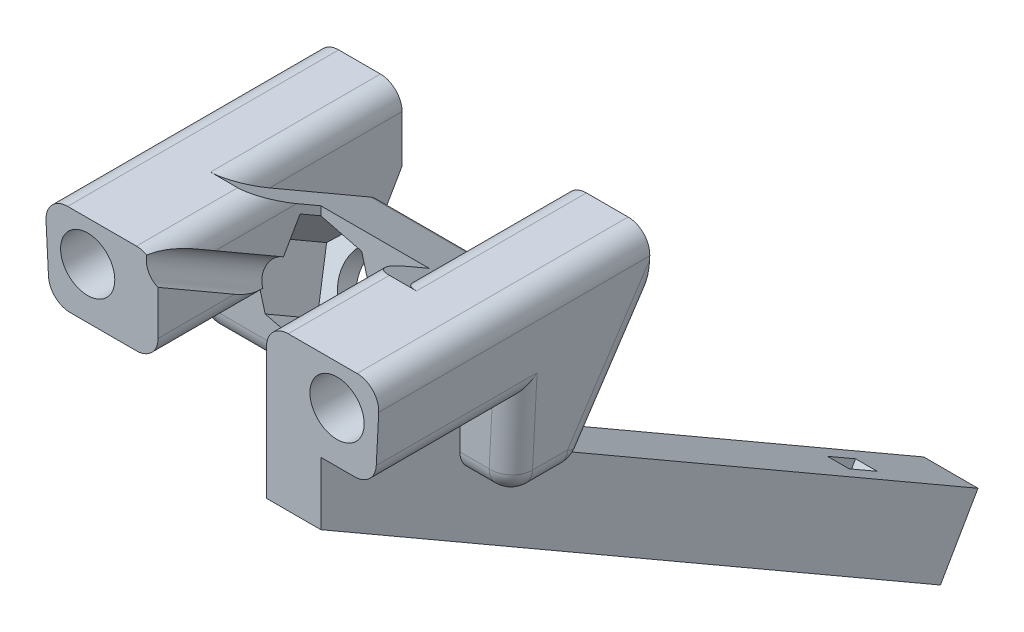
SolidWorks part; units mm, degrees
ref_plane "Alzado" through (0, 0, 0) normal (0, 0, 1) x (1, 0, 0)
ref_plane "Planta" through (0, 0, 0) normal (0, 1, 0) x (1, 0, 0)
ref_plane "Vista lateral" through (0, 0, 0) normal (1, 0, 0) x (0, 0, -1)
sketch "Croquis1" plane through (0, 0, 0) normal (0, 0, 1) x (1, 0, 0)
  line L0 (-15.1222, -77.6726) -> (-16.327, -54.7197)
  line L2 (15.1222, -77.6726) -> (16.327, -54.7197)
  line L4 (16.327, -54.7197) -> (-16.327, -54.7197)
  line L5 (-9.306, -78.3777) -> (-6.6466, -69.6276)
  line L6 (-3.7763, -67.5) -> (3.7763, -67.5)
  line L7 (6.6466, -69.6276) -> (9.306, -78.3777)
  circle A0 centre (-11.5, -75) radius 1.4876
  circle A1 centre (11.5, -75) radius 1.5
  arc A2 (-12.7397, -80.452) -> (-15.1222, -77.6726) centre (-12.1263, -77.5153) cw
  arc A3 (-12.7397, -80.452) -> (-9.306, -78.3777) centre (-12.1764, -77.5053) ccw
  arc A4 (-6.6466, -69.6276) -> (-3.7763, -67.5) centre (-3.7763, -70.5) cw
  arc A5 (3.7763, -67.5) -> (6.6466, -69.6276) centre (3.7763, -70.5) cw
  arc A6 (9.306, -78.3777) -> (12.7397, -80.452) centre (12.1764, -77.5053) ccw
  arc A7 (12.7397, -80.452) -> (15.1222, -77.6726) centre (12.1263, -77.5153) ccw
ref_plane "Plano1" through (0, 0, 0) normal (0, 0, 1) x (1, 0, 0)
sketch "Croquis2" plane through (0, 0, 0) normal (0, 0, 1) x (1, 0, 0)
  line L3 (15.4559, -71.3146) -> (-15.4559, -71.3146)
  line L4 (-3.7763, -67.5) -> (3.7763, -67.5) construction
  line L20 (15.1222, -77.6726) -> (15.4559, -71.3146)
  line L21 (-15.1222, -77.6726) -> (-14.5973, -87.6726)
  line L22 (15.1222, -77.6726) -> (6, -87.6726) construction
  line L23 (6, -87.6726) -> (-6, -87.6726)
  line L24 (0, -87.6726) -> (0, -67.5) construction
  line L25 (11.5, -72.5146) -> (11.5, -71.3146) construction
  line L26 (-11.5, -72.5146) -> (-11.5, -71.3146) construction
  line L27 (-15.1222, -77.6726) -> (-6, -87.6726) construction
  line L28 (-15.1222, -77.6726) -> (-15.4559, -71.3146)
  line L29 (-14.5973, -87.6726) -> (-6, -87.6726)
  line L30 (14.5973, -87.6726) -> (6, -87.6726)
  line L31 (15.1222, -77.6726) -> (14.5973, -87.6726)
  circle A4 centre (11.5, -75.0146) radius 2.5
  circle A5 centre (-11.5, -75.0146) radius 2.5
  point P11 (0, -78.4389)
  point P18 (0, -71.3146)
  dimension "D1" = 10
  dimension "D2" = 6
  dimension "D3" = 1.2
extrude "Saliente-Extruir1" add sketch "Croquis2" along normal blind 25
sketch "Croquis4" plane through (19.1465, -1.005, 0) normal (0.9986, -0.0524, 0) x (0, 0, -1)
  line L0 (5.0449, -68.0352) -> (5.0449, -99.8584)
  line L1 (5.0449, -99.8584) -> (-12.1656, -99.8584)
  line L2 (-9.729, -93.6242) -> (5.0449, -68.0352)
  line L4 (-25, -78.7869) -> (-25, -99.8584)
  line L5 (-25, -99.8584) -> (-12.1656, -99.8584)
  line L6 (-25, -78.7869) -> (-12.1656, -78.7869)
  line L8 (-12.1656, -78.7869) -> (-12.1656, -93.6242)
  line L9 (-12.1656, -93.6242) -> (-9.729, -93.6242)
  line L10 (0, -86.7869) -> (0, -70.4064) construction
  line L11 (-25, -86.7869) -> (0, -86.7869) construction
  point P10 (0, 0)
  point P11 (0, 0)
  point P12 (0, 0)
  point P15 (0, 0)
  dimension "D1" = 12.8344
  dimension "D2" = 30
  dimension "D3" = 12.1656
  dimension "D4" = 8
  dimension "D5" = 8
extrude "Cortar-Extruir1" cut sketch "Croquis4" along direction (1, 0, 0) on the side against the normal up to vertex (30.8693 mm away) up to point (-15.4559, -71.3146, 0)
sketch "Croquis5" plane through (0, -19.4582, -33.6563) normal (0, -0.5005, -0.8657) x (-1, 0, 0)
  line L0 (4.5973, -78.7943) -> (4.5973, -77.7943) construction
  line L2 (14.5973, -78.7943) -> (-14.5973, -78.7943) construction
  circle A0 centre (4.5973, -74.7943) radius 3
  point P4 (4.7149, -74.5677)
  point P5 (0, 0)
  point P6 (0, -74.7943)
  point P7 (0, 0)
  point P8 (7.1089, -74.0449)
  point P9 (0, 0)
  point P12 (7.5802, -74.7943)
  dimension "D1" = 1
  dimension "D2" = 6
  dimension "D3" = 10
extrude "Cortar-Extruir2" cut sketch "Croquis5" against normal blind 2
sketch "Croquis6" plane through (0, -18.4572, -31.9249) normal (0, -0.5005, -0.8657) x (-1, 0, 0)
  line L1 (3.0757, -79.5571) -> (7.9613, -78.4934)
  line L2 (7.9613, -78.4934) -> (9.4828, -73.7305)
  line L3 (9.4828, -73.7305) -> (6.1188, -70.0314)
  line L4 (6.1188, -70.0314) -> (1.2333, -71.0951)
  line L5 (1.2333, -71.0951) -> (-0.2883, -75.858)
  line L6 (-0.2883, -75.858) -> (3.0757, -79.5571)
  circle A0 centre (4.5973, -74.7943) radius 4.3301 construction
  dimension "D1" = 5
extrude "Cortar-Extruir3" cut sketch "Croquis6" against normal blind 10
sketch "Croquis8" plane through (0, -71.3146, 0) normal (0, 1, 0) x (1, 0, 0)
  line L2 (-5, -25) -> (5, -25)
  line L3 (-5, -25) -> (-5, -10)
  line L4 (-5, -10) -> (5, -10)
  line L5 (5, -25) -> (5, -10)
  line L11 (0, 0) -> (0, -25) construction
  line L12 (15.4559, 0) -> (-15.4559, 0) construction
  dimension "D1" = 5
  dimension "D2" = 15
  dimension "D3" = 10
extrude "Cortar-Extruir4" cut sketch "Croquis8" against normal blind 10
sketch "Croquis17" plane through (0, -19.4582, -33.6563) normal (0, -0.5005, -0.8657) x (-1, 0, 0)
  line L1 (-7.5, -61.0354) -> (7.5, -61.0354)
  line L2 (-7.5, -61.0354) -> (-7.5, -69.5824)
  line L3 (-7.5, -69.5824) -> (7.5, -69.5824)
  line L4 (7.5, -61.0354) -> (7.5, -69.5824)
  line L5 (0, -66.9256) -> (0, -56.6704) construction
  dimension "D1" = 15
  dimension "D2" = 7.5
extrude "Cortar-Extruir7" cut sketch "Croquis17" against normal blind 20
sketch "Croquis19" plane through (0, -19.4582, -33.6563) normal (0, -0.5005, -0.8657) x (-1, 0, 0)
  circle A0 centre (4.5973, -74.7943) radius 1.5
  dimension "D1" = 3
extrude "Cortar-Extruir9" cut sketch "Croquis19" against normal blind 30
sketch "Croquis20" plane through (5, -0.634, 0) normal (1, 0, 0) x (0, 0, -1)
  line L0 (-25, -78.7869) -> (-17.5618, -83.0813)
  line L1 (-12.1656, -79.0496) -> (-25, -79.0496) construction
  line L2 (-25, -79.0496) -> (-25, -70.6806) construction
  point P5 (0, 0)
  point P6 (0, 0)
  dimension "D1" = 30
sketch "Croquis21" plane through (0, 0, 25) normal (0, 0, 1) x (1, 0, 0)
  line L1 (10, -77.4689) -> (5, -77.4689)
  line L2 (10, -77.4689) -> (10, -85.4689)
  line L3 (10, -85.4689) -> (5, -85.4689)
  line L4 (5, -77.4689) -> (5, -85.4689)
  line L5 (5, -79.6836) -> (5, -71.3146) construction
  line L6 (5, -79.6836) -> (15.0166, -79.6836) construction
  point P4 (14, -77.5146)
  point P5 (0, 0)
  point P11 (0, 0)
  dimension "D1" = 8
  dimension "D2" = 5
extrude "Saliente-Extruir2" add sketch "Croquis21" along direction (0, -0.5, -0.866) on the side against the normal blind 70
fillet "Redondeo7" radius 2 19 edges at (-5, -79.6836, 20.0119) (0, -87.6726, 5.7815) (5, -71.3146, 20.3353) (7.5, -71.3146, 7.8353) (-5, -71.3146, 19.4337) (-7.5, -71.3146, 7.8353) (-15.4559, -71.3146, 12.5) (15.4559, -71.3146, 12.5) (0, -79.6976, 1.1708) (-14.8069, -83.6781, 12.1656) (-14.8597, -82.6726, 2.8907) (-14.5973, -87.6726, 8.9735) (-15.0166, -79.6836, 18.5828) (14.5973, -87.6726, 8.9735) (14.8597, -82.6726, 2.8907) (-4.7986, -87.6726, 12.1656) (12.2986, -87.6726, 12.1656) (14.8069, -83.6781, 12.1656) (15.0166, -79.6836, 18.5828)
sketch "Croquis27" plane through (10, 0, 0) normal (1, 0, 0) x (0, 0, -1)
  line L0 (36.1607, -111.5355) -> (31.3411, -119.8832)
  line L2 (31.3411, -119.8832) -> (36.1607, -120.6795)
  line L3 (36.1607, -120.6795) -> (36.1607, -111.5355)
  point P2 (0, 0)
  point P3 (31.104, -119.7463)
  point P5 (0, 0)
  point P8 (0, 0)
  point P9 (35.9236, -120.7097)
  point P10 (0, 0)
  point P11 (31.7781, -118.4729)
  dimension "D1" = 30
extrude "Cortar-Extruir13" cut sketch "Croquis27" against normal up to vertex (5 mm away) up to point (5, -112.4689, -35.6218)
sketch "Croquis28" plane through (0, -74.927, 43.2591) normal (0, -0.866, 0.5) x (1, 0, 0)
  line L0 (8.5, -78.0838) -> (8.5, -75.0838)
  line L1 (10, -87.0838) -> (10, -21.0838) construction
  line L2 (10, -87.0838) -> (5, -87.0838) construction
  line L3 (8.5, -78.0838) -> (6.5, -78.0838)
  line L4 (6.5, -78.0838) -> (6.5, -75.0838)
  line L5 (6.5, -75.0838) -> (8.5, -75.0838)
  dimension "D1" = 1.5
  dimension "D2" = 9
  dimension "D3" = 3
  dimension "D4" = 2
extrude "Cortar-Extruir14" cut sketch "Croquis28" against normal up to vertex (6.9282 mm away) up to point (10, -112.4689, -35.6218)
sketch "Croquis29" plane through (5, 0, 0) normal (-1, 0, 0) x (0, 0, 1)
  line L0 (21.1641, -79.6836) -> (12.1656, -79.6836)
  line L1 (12.1656, -79.6836) -> (12.1656, -84.8788)
  line L2 (12.1656, -84.8788) -> (21.1641, -79.6836)
extrude "Saliente-Extruir4" add sketch "Croquis29" against normal up to vertex (5 mm away) up to point (10, -84.8788, 12.1656)
